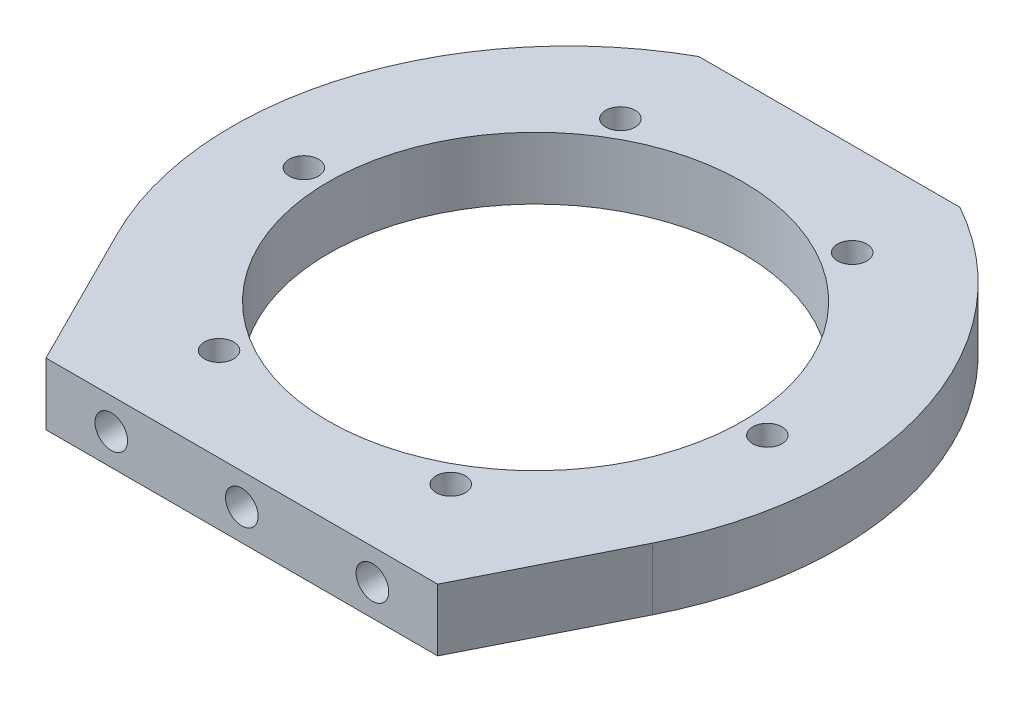
SolidWorks part; units mm, degrees
material "6061 Alloy"
ref_plane "Front Plane" through (0, 0, 0) normal (0, 0, 1) x (1, 0, 0)
ref_plane "Top Plane" through (0, 0, 0) normal (0, 1, 0) x (1, 0, 0)
ref_plane "Right Plane" through (0, 0, 0) normal (1, 0, 0) x (0, 0, -1)
sketch "Sketch1" plane through (0, 0, 0) normal (0, 1, 0) x (1, 0, 0)
  line L5 (0, 0) -> (0, -45) construction
  line L6 (-30, -45) -> (30, -45)
  line L7 (-20, 45) -> (20, 45)
  line L8 (0, 45) -> (0, 0) construction
  line L9 (-40.9978, -23.1128) -> (-30, -45)
  line L11 (5, 0) -> (0, 0) construction
  line L12 (40.9978, -23.1128) -> (30, -45)
  circle A2 centre (0, 0) radius 39.5 construction
  arc A5 (-20, 45) -> (-40.9978, -23.1128) centre (5, 0) ccw
  arc A6 (20, 45) -> (40.9978, -23.1128) centre (-5, 0) cw
  dimension "D1" = 45
  dimension "D3" = 45
  dimension "D4" = 40
  dimension "D2" = 79
  dimension "D6" = 5
  dimension "D5" = 60
extrude "3/8inch" add sketch "Sketch1" along normal mid plane 9.525
sketch "Sketch2" plane through (0, 4.7625, 0) normal (0, 1, 0) x (1, 0, 0)
  circle A0 centre (0, 0) radius 31.75
  dimension "D1" = 63.5
extrude "Cut-Extrude1" cut sketch "Sketch2" against normal up to surface (9.525 mm away) up to face at (0, -4.7625, 6.297)
sketch "Sketch3" plane through (0, 4.7625, 0) normal (0, 1, 0) x (1, 0, 0)
  line L0 (17.75, 30.7439) -> (0, 0) construction
  line L1 (20, 45) -> (-20, 45) construction
  circle A0 centre (0, 0) radius 35.5 construction
  circle A1 centre (17.75, 30.7439) radius 2.25
  circle A2 centre (35.5, 0) radius 2.25
  circle A3 centre (17.75, -30.7439) radius 2.25
  circle A4 centre (-17.75, -30.7439) radius 2.25
  circle A5 centre (-35.5, 0) radius 2.25
  circle A6 centre (-17.75, 30.7439) radius 2.25
  point P17 (0, 0)
  dimension "D1" = 71
  dimension "D2" = 4.5
  dimension "D4" = 120
  dimension "D3" = 6
extrude "M4_through" cut sketch "Sketch3" against normal up to surface (9.525 mm away) up to face at (0, -4.7625, -31.75)
sketch "Sketch4" plane through (0, 0, -45) normal (0, 0, -1) x (-1, 0, 0)
  line L0 (0, -4.7625) -> (0, 4.7625) construction
  line L1 (-20, 4.7625) -> (20, 4.7625) construction
  line L2 (0, 0) -> (-12, 0) construction
  line L3 (-20, -4.7625) -> (20, -4.7625) construction
  circle A0 centre (-12, 0) radius 2.5
  circle A1 centre (12, 0) radius 2.5
  dimension "D1" = 5
  dimension "D2" = 12
extrude "M5x8_DRILL" cut sketch "Sketch4" against normal blind 8
sketch "Sketch5" plane through (0, 0, 45) normal (0, 0, 1) x (1, 0, 0)
  line L0 (0, -4.7625) -> (0, 4.7625) construction
  line L1 (-30, 4.7625) -> (30, 4.7625) construction
  line L2 (0, 0) -> (-20, 0) construction
  line L3 (-30, -4.7625) -> (30, -4.7625) construction
  circle A0 centre (-20, 0) radius 2.5
  circle A1 centre (20, 0) radius 2.5
  circle A2 centre (0, 0) radius 2.5
  dimension "D1" = 5
  dimension "D2" = 20
extrude "M5x8_DRILL2" cut sketch "Sketch5" against normal blind 8
